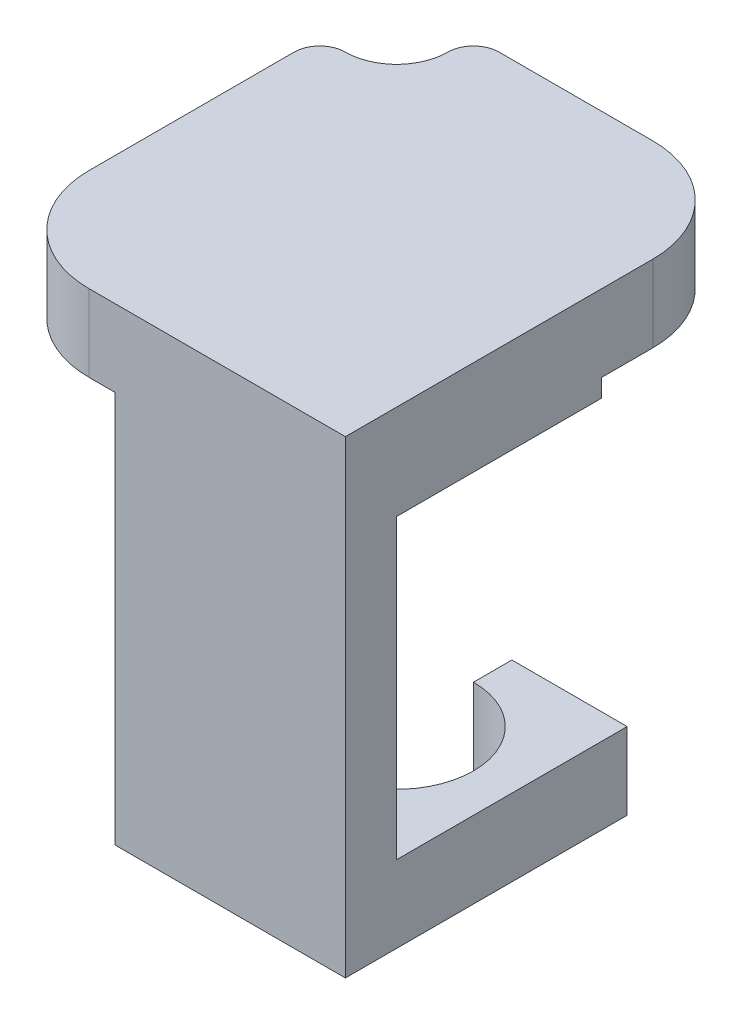
SolidWorks part; units mm, degrees
ref_plane "Plan de face" through (0, 0, 0) normal (0, 0, 1) x (1, 0, 0)
ref_plane "Plan de dessus" through (0, 0, 0) normal (0, 1, 0) x (1, 0, 0)
ref_plane "Plan de droite" through (0, 0, 0) normal (1, 0, 0) x (0, 0, -1)
sketch "Esquisse1" plane through (0, 0, 0) normal (0, 1, 0) x (1, 0, 0)
  line L1 (-13.3528, 14.2841) -> (-4.3528, 14.2841)
  line L2 (-13.3528, 14.2841) -> (-13.3528, 5.2841)
  line L3 (-13.3528, 5.2841) -> (-4.3528, 5.2841)
  line L4 (-4.3528, 14.2841) -> (-4.3528, 5.2841)
  line L5 (-13.3528, 14.2841) -> (-4.3528, 5.2841) construction
  line L6 (-13.3528, 5.2841) -> (-4.3528, 14.2841) construction
  point P0 (-8.8528, 9.7841)
  dimension "D1" = 9
  dimension "D2" = 9
extrude "Boss.-Extru.1" add sketch "Esquisse1" against normal blind 3
sketch "Esquisse2" plane through (0, -3, 0) normal (0, -1, 0) x (1, 0, 0)
  line L0 (-8.8528, -12.7841) -> (-8.8528, -14.2841)
  line L1 (-4.3528, -14.2841) -> (-13.3528, -14.2841) construction
  line L2 (-8.8528, -14.2841) -> (-13.3528, -14.2841)
  line L3 (-13.3528, -14.2841) -> (-13.3528, -5.2841) construction
  line L4 (-13.3528, -14.2841) -> (-13.3528, -9.7841)
  line L5 (-13.3528, -9.7841) -> (-11.8528, -9.7841)
  arc A0 (-8.8528, -12.7841) -> (-11.8528, -9.7841) centre (-8.8528, -9.7841) ccw
  dimension "D1" = 6
extrude "Enlèv. mat.-Extru.1" cut sketch "Esquisse2" against normal through all
sketch "Esquisse3" plane through (0, 0, -5.2841) normal (0, 0, 1) x (1, 0, 0)
  line L0 (-4.3528, -3) -> (-4.3528, 0) construction
  line L1 (-13.3528, -3) -> (-4.3528, -3)
  line L2 (-13.3528, -3) -> (-13.3528, 15.3)
  line L3 (-13.3528, 15.3) -> (-4.3528, 15.3)
  line L4 (-4.3528, -3) -> (-4.3528, 15.3)
  line L5 (-13.3528, -3) -> (-4.3528, -3) construction
  line L8 (-220.3528, 11.3) -> (-6.3528, 11.3) construction
  dimension "D1" = 4
extrude "Boss.-Extru.3" add sketch "Esquisse3" along normal blind 2
sketch "Esquisse4" plane through (0, 0, -5.2841) normal (0, 0, -1) x (-1, 0, 0)
  line L0 (13.3528, 15.3) -> (13.3528, 0) construction
  line L1 (4.3528, 15.3) -> (13.3528, 15.3)
  line L2 (4.3528, 15.3) -> (4.3528, 11.6)
  line L3 (4.3528, 11.6) -> (13.3528, 11.6)
  line L4 (13.3528, 15.3) -> (13.3528, 11.6)
  line L6 (220.3528, 11.3) -> (6.3528, 11.3) construction
  dimension "D1" = 0.3
extrude "Boss.-Extru.4" add sketch "Esquisse4" along normal blind 8 contours L3 L4 L1 L2
sketch "Esquisse8" plane through (0, 15.3, 0) normal (0, 1, 0) x (1, 0, 0)
  line L0 (-18.3528, 3.2841) -> (-4.3528, 3.2841)
  line L1 (-18.3528, 3.2841) -> (-18.3528, 14.2841)
  line L2 (-18.3528, 14.2841) -> (-13.3528, 14.2841)
  line L3 (-13.3528, 14.2841) -> (-13.3528, 19.2841)
  line L4 (-13.3528, 19.2841) -> (-4.3528, 19.2841)
  line L5 (-4.3528, 19.2841) -> (-4.3528, 3.2841)
  line L7 (-6.3528, 7.2841) -> (-6.3528, 221.2841) construction
  line L8 (-220.3528, 7.2841) -> (-6.3528, 7.2841) construction
  dimension "D1" = 14
  dimension "D2" = 16
  dimension "D3" = 7
  dimension "D5" = 7
extrude "Boss.-Extru.6" add sketch "Esquisse8" against normal blind 3
sketch "Esquisse9" plane through (0, 15.3, 0) normal (0, 1, 0) x (1, 0, 0)
  line L2 (-18.3528, 16.2841) -> (-18.3528, 3.2841)
  line L3 (-18.3528, 3.2841) -> (-4.3528, 3.2841)
  line L4 (-13.3528, 19.2841) -> (-13.3528, 14.2841) construction
  line L5 (-13.3528, 14.2841) -> (-18.3528, 14.2841) construction
  line L6 (-15.3528, 19.2841) -> (-15.3528, 16.2841)
  line L7 (-15.3528, 16.2841) -> (-18.3528, 16.2841)
  line L8 (-4.3528, 3.2841) -> (-4.3528, 19.2841)
  line L9 (-4.3528, 19.2841) -> (-15.3528, 19.2841)
  dimension "D2" = 2
  dimension "D1" = 2
extrude "Boss.-Extru.8" add sketch "Esquisse9" against normal up to surface (1 mm away)
fillet "Congé2" radius 4 2 edges at (-4.3528, 13.8, -19.2841) (-18.3528, 13.8, -3.2841)
fillet "Congé3" radius 2 1 edges at (-15.3528, 14.8, -16.2841)
sketch "Esquisse6" plane through (0, 15.3, 0) normal (0, 1, 0) x (1, 0, 0)
  line L0 (-4.3528, 3.2841) -> (-4.3528, 21.2841)
  line L1 (-4.3528, 3.2841) -> (-4.3528, 15.2841) construction
  line L2 (-4.3528, 3.2841) -> (-22.3528, 3.2841)
  arc A0 (-4.3528, 21.2841) -> (-22.3528, 3.2841) centre (-7.7404, 6.6716) ccw
  dimension "D3" = 15
  dimension "D1" = 18
  dimension "D2" = 18
sketch "Esquisse7" plane through (0, 11.6, 0) normal (0, -1, 0) x (1, 0, 0)
  circle A0 centre (-8.8528, -9.7841) radius 1.33
extrude "Enlèv. mat.-Extru.2" cut sketch "Esquisse7" against normal blind 1
fillet "Congé4" radius 1 2 edges at (-15.3528, 14.8, -19.2841) (-18.3528, 14.8, -16.2841)
